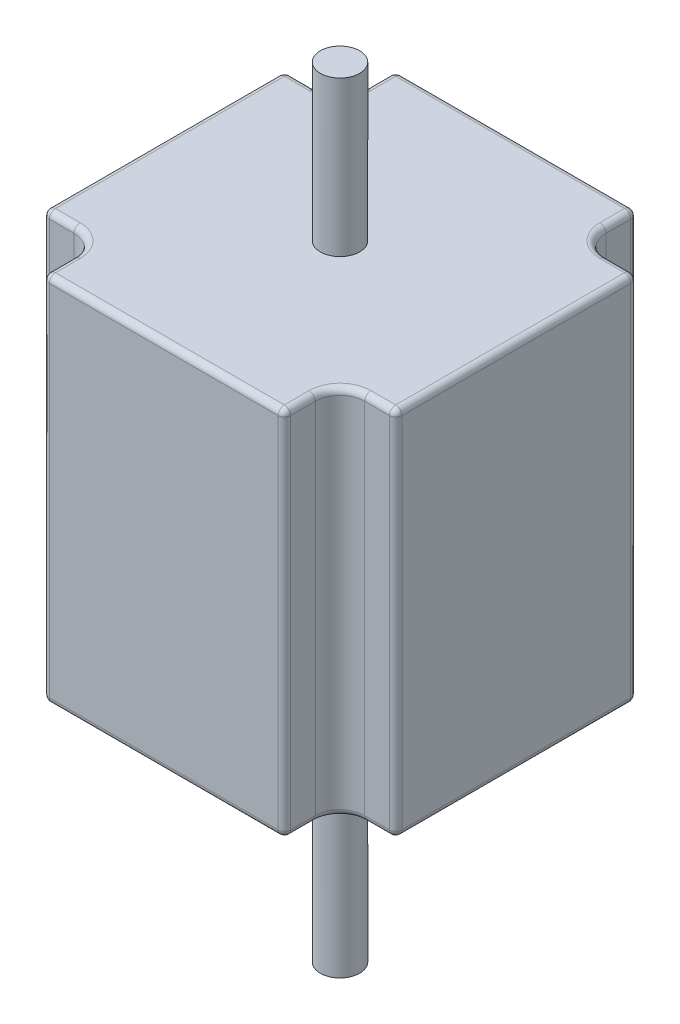
SolidWorks part; units mm, degrees
note: '?' marks a value the reader was unsure of.
material "Cast Alloy Steel"
ref_plane "Front" through (0, 0, 0) normal (0, 0, 1) x (1, 0, 0)
ref_plane "Top" through (0, 0, 0) normal (0, 1, 0) x (1, 0, 0)
ref_plane "Right" through (0, 0, 0) normal (1, 0, 0) x (0, 0, -1)
ref_axis "Axis1" through (-84.4107, 0, 0) along (1, 0, 0)?
ref_axis "Axis2" through (0, 64.3378, 0) along (0, -1, 0)?
ref_axis "Axis3" through (0, 0, -102.329) along (0, 0, 1)?
sketch "Sketch1" plane through (0, 0, 0) normal (0, 1, 0) x (1, 0, 0)
  line L1 (-28.5, -28.5) -> (28.5, -28.5)
  line L2 (-28.5, -28.5) -> (-28.5, 28.5)
  line L3 (-28.5, 28.5) -> (28.5, 28.5)
  line L4 (28.5, -28.5) -> (28.5, 28.5)
  line L5 (-28.5, -28.5) -> (28.5, 28.5) construction
  line L6 (-28.5, 28.5) -> (28.5, -28.5) construction
  point P0 (0, 0)
  dimension "D1" = 57
  dimension "D2" = 57
extrude "Extrude1" add sketch "Sketch1" along normal blind 60
hole_wizard "Ø5.0 (5) Diameter Hole1" positions "Sketch5" profile "Sketch4" hole size "Ø5.0" standard "ISO" end condition through all
sketch "Sketch5" plane through (0, 0, 0) normal (0, -1, 0) x (1, 0, 0)
  line L0 (-28.5, 28.5) -> (28.5, -28.5) construction
  line L3 (28.5, 28.5) -> (-28.5, -28.5) construction
  point P0 (-23.5, 23.5)
  point P1 (23.5, 23.5)
  point P3 (23.5, -23.5)
  point P5 (-23.5, -23.5)
  dimension "D1" = 47
  dimension "D2" = 47
sketch "Sketch4" plane through (-23.5, 0, 23.5) normal (1, 0, 0) x (0, 0, -1)
  line L0 (0, 0) -> (0, 60)
  line L1 (0, 60) -> (2.5, 60)
  line L2 (2.5, 60) -> (2.5, 0)
  line L5 (2.5, 0) -> (0, 0)
  line L11 (0, -6.35) -> (0, 107.95) construction
  dimension "Thru Hole Dia." = 5
  dimension "Thru Hole Depth" = 60
sketch "Sketch6" plane through (0, 60, 0) normal (0, 1, 0) x (1, 0, 0)
  line L0 (-19.5, 23.5) -> (-19.5, 32.5117)
  line L1 (-19.5, 32.5117) -> (-33.9089, 32.5117)
  line L2 (-33.9089, 32.5117) -> (-33.9089, 19.5)
  line L3 (-33.9089, 19.5) -> (-23.5, 19.5)
  line L4 (19.5, 23.5) -> (19.5, 36.4716)
  line L5 (19.5, 36.4716) -> (41.1684, 36.4716)
  line L6 (41.1684, 36.4716) -> (41.1684, 19.5)
  line L7 (41.1684, 19.5) -> (23.5, 19.5)
  line L8 (23.5, -19.5) -> (44.2522, -19.5)
  line L9 (44.2522, -19.5) -> (44.2522, -40.0504)
  line L10 (44.2522, -40.0504) -> (19.5, -40.0504)
  line L11 (19.5, -40.0504) -> (19.5, -23.5)
  line L12 (-23.5, -19.5) -> (-37.6708, -19.5)
  line L13 (-37.6708, -19.5) -> (-37.6708, -37.8282)
  line L14 (-37.6708, -37.8282) -> (-19.5, -37.8282)
  line L15 (-19.5, -37.8282) -> (-19.5, -23.5)
  circle A0 centre (-23.5, 23.5) radius 4
  circle A1 centre (23.5, 23.5) radius 4
  circle A2 centre (23.5, -23.5) radius 4
  circle A3 centre (-23.5, -23.5) radius 4
  circle M1 centre (-23.5, -23.5) radius 2.5
  circle M2 centre (23.5, -23.5) radius 2.5
  circle M3 centre (23.5, 23.5) radius 2.5
  circle M4 centre (-23.5, 23.5) radius 2.5
  line M5 (28.5, -28.5) -> (28.5, 28.5)
  line M6 (28.5, 28.5) -> (-28.5, 28.5)
  line M7 (-28.5, 28.5) -> (-28.5, -28.5)
  line M8 (-28.5, -28.5) -> (28.5, -28.5)
  dimension "D1" = 8
  dimension "D2" = 8
  dimension "D3" = 8
  dimension "D4" = 8
extrude "Extrude4" cut sketch "Sketch6" against normal blind 71 contours L2 L3 L0 L1 M7 M6 | A0 L0 L3 M6 M7 | A0 M4 | L7 L6 L5 L4 M6 M5 | A1 L7 L4 M5 M6 | A1 M3 | A2 M2 | A2 L11 L8 M8 M5 | L11 L10 L9 L8 M5 M8 | L14 L15 L12 L13 M8 M7 | A3 L12 L15 M7 M8 | A3 M1
fillet "Fillet1" radius 1 16 edges at (26, 0, -19.5) (19.5, 0, -26) (19.5, 0, 26) (26, 0, 19.5) (-26, 0, 19.5) (-19.5, 0, 26) (20.6716, 0, -20.6716) (0, 0, -28.5) (28.5, 0, 0) (20.6716, 0, 20.6716) (0, 0, 28.5) (-20.6716, 0, 20.6716) (-28.5, 0, 0) (-19.5, 0, -26) (-26, 0, -19.5) (-20.6716, 0, -20.6716)
sketch "Sketch7" plane through (0, 60, 0) normal (0, 1, 0) x (1, 0, 0)
  circle A0 centre (0, 0) radius 3.175
  dimension "D1" = 6.35
extrude "Extrude5" add sketch "Sketch7" along normal blind 25 and the other way blind 101 separate body
sketch "Sketch8" plane through (0, 0, 0) normal (0, -1, 0) x (1, 0, 0)
  circle A0 centre (0, 0) radius 15
  dimension "D1" = 30
extrude "Extrude6" add sketch "Sketch8" along normal blind 3
fillet "Fillet2" radius 1 32 edges at (-26, 60, 19.5) (-20.6716, 60, 20.6716) (-19.5, 60, 26) (0, 60, 28.5) (19.5, 60, 26) (20.6716, 60, 20.6716) (26, 60, 19.5) (28.5, 60, 0) (19.5, 60, -26) (26, 60, -19.5) (20.6716, 60, -20.6716) (-26, 60, -19.5) (-19.5, 60, -26) (-20.6716, 60, -20.6716) (0, 60, -28.5) (-28.5, 60, 0) (-19.5, 30.5, 28.5) (-28.5, 30.5, 19.5) (-28.5, 30.5, -19.5) (-19.5, 30.5, -28.5) (19.5, 30.5, -28.5) (28.5, 30.5, -19.5) (28.5, 30.5, 19.5) (19.5, 30.5, 28.5) (-19.2071, 0.2929, 28.2071) (-28.2071, 0.2929, 19.2071) (19.2071, 0.2929, -28.2071) (28.2071, 0.2929, -19.2071) (28.2071, 0.2929, 19.2071) (19.2071, 0.2929, 28.2071) (-28.2071, 0.2929, -19.2071) (-19.2071, 0.2929, -28.2071)
